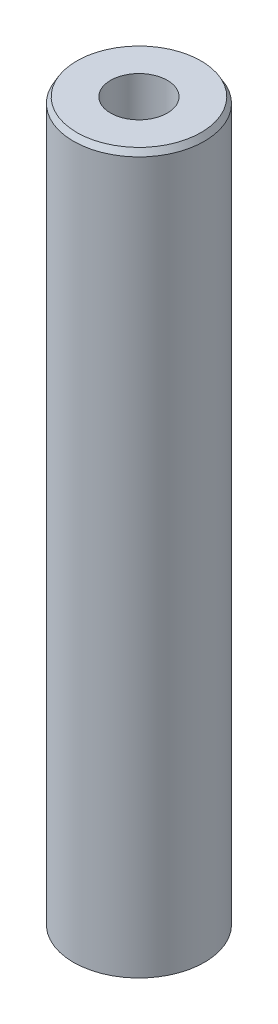
SolidWorks part; units mm, degrees
ref_plane "Front Plane" through (0, 0, 0) normal (0, 0, 1) x (1, 0, 0)
ref_plane "Top Plane" through (0, 0, 0) normal (0, 1, 0) x (1, 0, 0)
ref_plane "Right Plane" through (0, 0, 0) normal (1, 0, 0) x (0, 0, -1)
sketch "Sketch1" plane through (0, 0, 0) normal (0, 1, 0) x (1, 0, 0)
  circle A0 centre (0, 0) radius 7.5
  dimension "SHAFT_OD" = 15
extrude "Boss-Extrude1" add sketch "Sketch1" along normal blind 82.5
sketch "Sketch2" plane through (0, 0, 0) normal (0, 1, 0) x (1, 0, 0)
  circle A0 centre (0, 0) radius 3.2515
  dimension "BORE_D" = 6.503
extrude "Cut-Extrude1" cut sketch "Sketch2" along normal through all
chamfer "Chamfer1" distance 0.6715 angle 30 2 edges at (0, 82.5, 7.5) (0, 0, 7.5) first distance on face at (0, 82.5, 7.5) first distance on face at (0, 0, 3.2515)
